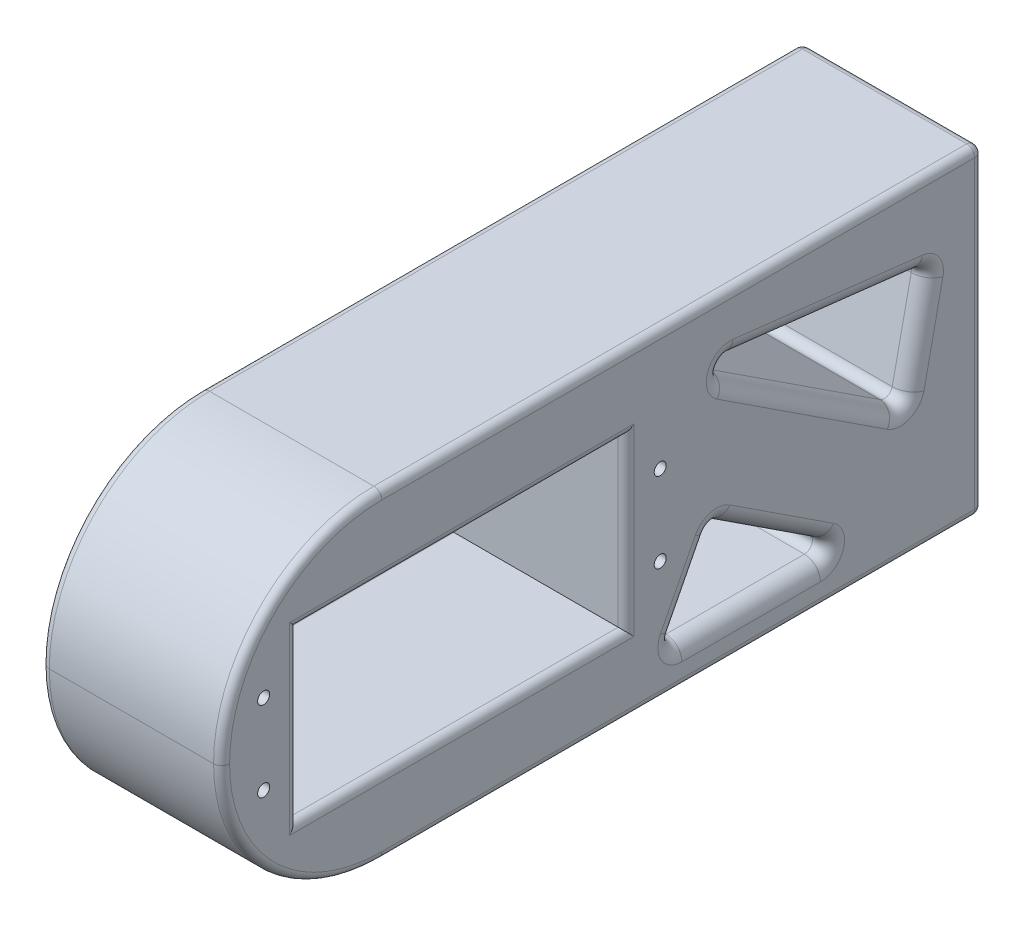
SolidWorks part; units mm, degrees
material "ABS"
ref_plane "Front Plane" through (0, 0, 0) normal (0, 0, 1) x (1, 0, 0)
ref_plane "Top Plane" through (0, 0, 0) normal (0, 1, 0) x (1, 0, 0)
ref_plane "Right Plane" through (0, 0, 0) normal (1, 0, 0) x (0, 0, -1)
sketch "Sketch4" plane through (0, 0, 0) normal (0, 1, 0) x (1, 0, 0)
  line L17 (-16.25, 20) -> (-5, 20)
  line L20 (-5, 20) -> (6.25, 20)
  line L21 (-16.25, -75) -> (-5, -75)
  line L22 (-5, -75) -> (6.25, -75)
  line L23 (6.25, 20) -> (6.25, -75)
  line L24 (-16.25, 20) -> (-16.25, -75)
extrude "MBODY" add sketch "Sketch4" along normal blind 40 contours L17 L20 L23 L22 L21 L24
sketch "Sketch5" plane through (0, 0, -20) normal (0, 0, -1) x (-1, 0, 0)
  line L3 (0, 20) -> (0, 15)
  line L4 (0, 20) -> (0, 25)
  line L5 (0, 25) -> (10, 25)
  line L6 (10, 25) -> (10, 35)
  line L7 (10, 35) -> (0, 35)
  line L8 (0, 15) -> (10, 15)
  line L9 (10, 15) -> (10, 5)
  line L10 (10, 5) -> (0, 5)
  circle A1 centre (0, 5) radius 0.75
  circle A2 centre (10, 5) radius 0.75
  circle A3 centre (10, 15) radius 0.75
  circle A4 centre (0, 15) radius 0.75
  circle A5 centre (0, 25) radius 0.75
  circle A6 centre (10, 25) radius 0.75
  circle A7 centre (10, 35) radius 0.75
  circle A8 centre (0, 35) radius 0.75
extrude "FrontScrews" cut sketch "Sketch5" against normal blind 3 contours A8 | A7 | A6 | A5 | A4 | A3 | A1 | A2
sketch "Sketch7" plane through (0, 0, -20) normal (0, 0, -1) x (-1, 0, 0)
  circle A0 centre (5, 20) radius 2.75
extrude "GUIDKNOB" add sketch "Sketch7" along normal blind 4 contours A0
sketch "Sketch10" plane through (6.25, 0, 0) normal (1, 0, 0) x (0, 0, -1)
  line L1 (-65.5, 20) -> (-65.5, 30.5)
  line L2 (-65.5, 20) -> (-65.5, 9.5)
  line L3 (-65.5, 30.5) -> (-24.5, 30.5)
  line L4 (-65.5, 9.5) -> (-24.5, 9.5)
  line L5 (-24.5, 9.5) -> (-24.5, 30.5)
  point P0 (-45, 30.5)
extrude "ServoCut" cut sketch "Sketch10" against normal blind 40.5 contours L4 L5 L3 L1 L2
fillet "RoundEnd" radius 20 2 edges at (-5, 0, 75) (-5, 40, 75)
sketch "Sketch15" plane through (6.25, 33.75, 0) normal (-1, 0, 0) x (0, 1, 0)
  line L0 (-8.75, -69.75) -> (-8.75, -65)
  line L1 (-18.75, -65) -> (-18.75, -69.75)
  line L2 (-18.75, -69.75) -> (-8.75, -69.75)
  line L3 (-8.75, -20.25) -> (-18.75, -20.25)
  line L6 (-18.75, -25) -> (-18.75, -20.25)
  circle A0 centre (-18.75, -69.75) radius 0.75
  circle A1 centre (-8.75, -69.75) radius 0.75
  circle A2 centre (-8.75, -20.25) radius 0.75
  circle A3 centre (-18.75, -20.25) radius 0.75
extrude "ServoScrews" cut sketch "Sketch15" along normal blind 3 contours A1 | A0 | A2 | A3
fillet "EDGES1MM" radius 1 20 edges at (6.25, 5.8579, 69.1421) (6.25, 34.1421, 69.1421) (-5, 0, -20) (6.25, 0, 17.5) (-5, 40, -20) (6.25, 40, 17.5) (-16.25, 30.5, 45) (-16.25, 20, 24.5) (-16.25, 9.5, 45) (-16.25, 20, 65.5) (-16.25, 20, -20) (-16.25, 40, 17.5) (-16.25, 34.1421, 69.1421) (-16.25, 5.8579, 69.1421) (-16.25, 0, 17.5) (6.25, 9.5, 45) (6.25, 20, 65.5) (6.25, 30.5, 45) (6.25, 20, 24.5) (6.25, 20, -20)
sketch "Sketch20" plane through (-16.25, 0, 0) normal (-1, 0, 0) x (0, 0, 1)
  line L0 (-12.2152, 29.7463) -> (11.3834, 32.4738)
  line L1 (12.0453, 30.6434) -> (-9.1815, 16.7689)
  line L2 (-10.7067, 17.3978) -> (-13.0785, 28.5449)
  line L3 (12.6592, 15.0777) -> (-0.2906, 6.6133)
  line L4 (0.2566, 4.7762) -> (17.5439, 4.7762)
  line L5 (18.4339, 6.2323) -> (14.0963, 14.6967)
  arc A0 (14.0963, 14.6967) -> (12.6592, 15.0777) centre (13.2063, 14.2406) ccw
  arc A1 (17.5439, 4.7762) -> (18.4339, 6.2323) centre (17.5439, 5.7762) ccw
  arc A2 (0.2566, 4.7762) -> (-0.2906, 6.6133) centre (0.2566, 5.7762) cw
  arc A3 (12.0453, 30.6434) -> (11.3834, 32.4738) centre (11.4982, 31.4804) ccw
  arc A4 (-10.7067, 17.3978) -> (-9.1815, 16.7689) centre (-9.7286, 17.6059) ccw
  arc A5 (-13.0785, 28.5449) -> (-12.2152, 29.7463) centre (-12.1004, 28.753) cw
  dimension "D1" = 1
extrude "Cut-Extrude2" cut sketch "Sketch20" against normal blind 25
fillet "Fillet5" radius 2 24 edges at (-16.25, 15.2072, 13.4626) (-16.25, 10.4645, 16.2651) (-16.25, 5.2547, 18.3972) (-16.25, 4.7762, 8.9002) (-16.25, 5.4908, -0.7018) (-16.25, 16.6814, -10.1099) (-16.25, 22.9713, -11.8926) (-16.25, 29.3365, -12.9125) (-16.25, 31.1101, -0.4159) (-16.25, 31.8205, 12.4386) (6.25, 31.8205, 12.4386) (6.25, 31.1101, -0.4159) (6.25, 29.3365, -12.9125) (6.25, 22.9713, -11.8926) (6.25, 16.6814, -10.1099) (6.25, 15.2072, 13.4626) (6.25, 10.8455, 6.1843) (6.25, 5.4908, -0.7018) (6.25, 4.7762, 8.9002) (6.25, 5.2547, 18.3972) (-16.25, 10.8455, 6.1843) (-16.25, 23.7061, 1.4319) (6.25, 23.7061, 1.4319) (6.25, 10.4645, 16.2651)
equation "\"3.5.00mm\"=5"
